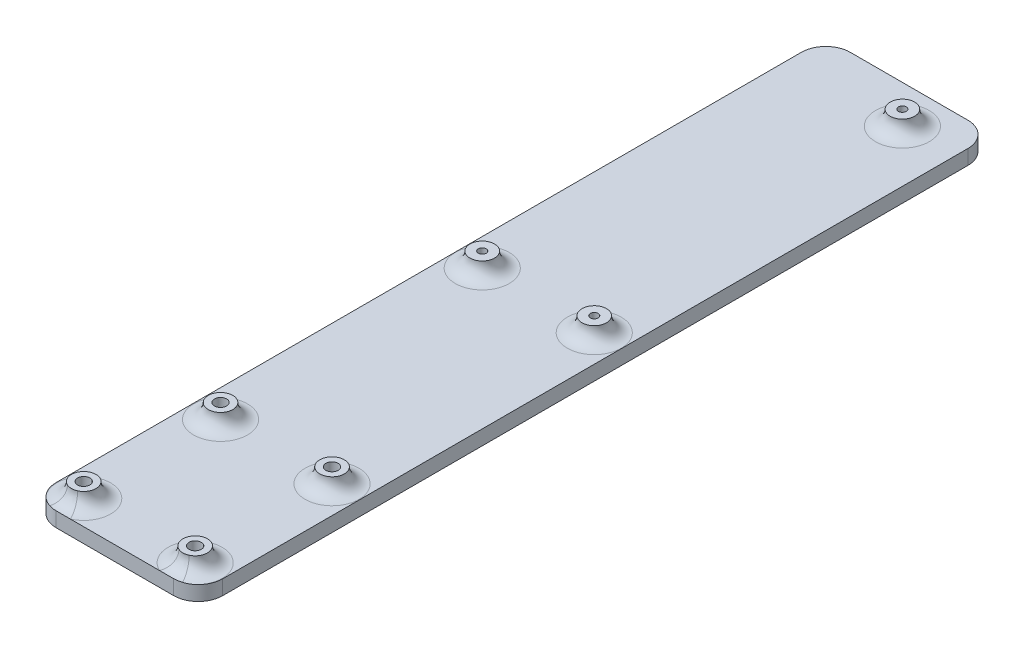
SolidWorks part; units mm, degrees
ref_plane "Front Plane" through (0, 0, 0) normal (0, 0, 1) x (1, 0, 0)
ref_plane "Top Plane" through (0, 0, 0) normal (0, 1, 0) x (1, 0, 0)
ref_plane "Right Plane" through (0, 0, 0) normal (1, 0, 0) x (0, 0, -1)
sketch "Sketch1" plane through (0, 0, 0) normal (0, 1, 0) x (1, 0, 0)
  line L0 (11.4254, -21.605) -> (-11.4346, -21.605) construction
  line L1 (14, -49.075) -> (-14, -49.075)
  line L2 (14, -49.075) -> (14, 49.075)
  line L3 (14, 49.075) -> (-14, 49.075)
  line L4 (-14, -49.075) -> (-14, 49.075)
  line L5 (14, -49.075) -> (-14, 49.075) construction
  line L6 (14, 49.075) -> (-14, -49.075) construction
  line L7 (0, -89.04) -> (0, 0) construction
  line L8 (-11.375, -75.075) -> (11.375, -75.075)
  line L9 (-11.375, -75.075) -> (-11.375, -103.005)
  line L10 (-11.375, -103.005) -> (11.375, -103.005)
  line L11 (11.375, -75.075) -> (11.375, -103.005)
  line L12 (-11.375, -75.075) -> (11.375, -103.005) construction
  line L13 (-11.375, -103.005) -> (11.375, -75.075) construction
  line L15 (-9, -49.075) -> (9, -49.075)
  line L16 (-9, -49.075) -> (-9, -55.075)
  line L17 (-9, -55.075) -> (9, -55.075)
  line L18 (9, -49.075) -> (9, -55.075)
  point P0 (0, 0)
  point P6 (11.4254, -21.605)
  point P7 (-11.4346, -21.605)
  point P10 (0, -89.04)
  point P12 (6.36, 46.345)
  point P22 (0, -55.075)
  dimension "D1" = 28
  dimension "D2" = 98.15
  dimension "D3" = 2.5654
  dimension "D4" = 25.4254
  dimension "D5" = 70.68
  dimension "D6" = 7.64
  dimension "D7" = 2.73
  dimension "D8" = 22.75
  dimension "D9" = 27.93
  dimension "D10" = 20
  dimension "D11" = 18
  dimension "D12" = 6
sketch "Sketch3" plane through (0, 0, 0) normal (0, 1, 0) x (1, 0, 0)
  line L0 (14, 49.075) -> (-14, 49.075) construction
  line L1 (-17, 54.075) -> (17, 54.075)
  line L2 (-17, 54.075) -> (-17, -108.005)
  line L3 (-17, -108.005) -> (17, -108.005)
  line L4 (17, 54.075) -> (17, -108.005)
  line L5 (14, -49.075) -> (14, 49.075) construction
  line L6 (-11.375, -103.005) -> (11.375, -103.005) construction
  line L7 (-14, -49.075) -> (-14, 49.075) construction
  dimension "D1" = 5
  dimension "D2" = 3
  dimension "D3" = 5
  dimension "D4" = 3
extrude "Boss-Extrude1" add sketch "Sketch3" along normal blind 3
sketch "Sketch4" plane through (0, 3, 0) normal (0, 1, 0) x (1, 0, 0)
  circle A0 centre (6.36, 46.345) radius 2.5
  circle A1 centre (-11.4346, -21.605) radius 2.5
  circle A2 centre (11.4254, -21.605) radius 2.5
  circle A3 centre (-11.375, -75.075) radius 2.5
  circle A4 centre (-11.375, -103.005) radius 2.5
  circle A5 centre (11.375, -103.005) radius 2.5
  circle A6 centre (11.375, -75.075) radius 2.5
  dimension "D1" = 5
extrude "Boss-Extrude2" add sketch "Sketch4" along normal blind 3
fillet "Fillet1" radius 3 7 edges at (11.375, 3, 77.575) (11.375, 3, 105.505) (-11.375, 3, 105.505) (-11.375, 3, 77.575) (6.36, 3, -43.845) (11.4254, 3, 24.105) (-11.4346, 3, 24.105)
hole_wizard "Tap Drill for M2x0.4 Tap1" positions "Sketch7" profile "Sketch8" hole size "M2x0.4" standard "ANSI Metric" end condition through all
sketch "Sketch7" plane through (0, 6, 0) normal (0, 1, 0) x (1, 0, 0)
  point P0 (6.36, 46.345)
  point P3 (-11.4346, -21.605)
  point P6 (11.4254, -21.605)
sketch "Sketch8" plane through (6.36, 6, -46.345) normal (1, 0, 0) x (0, 0, 1)
  line L0 (0, 0) -> (0, 6)
  line L1 (0, 6) -> (0.8, 6)
  line L2 (0.8, 6) -> (0.8, 0)
  line L5 (0.8, 0) -> (0, 0)
  line L11 (0, -6.35) -> (0, 107.95) construction
  dimension "Thru Hole Dia." = 1.6
  dimension "Thru Hole Depth" = 6
hole_wizard "Tap Drill for M3x0.5 Tap1" positions "Sketch5" profile "Sketch6" hole size "M3x0.5" standard "ANSI Metric" end condition through all
sketch "Sketch5" plane through (0, 6, 0) normal (0, 1, 0) x (1, 0, 0)
  point P9 (-11.375, -75.075)
  point P12 (-11.375, -103.005)
  point P15 (11.375, -103.005)
  point P18 (11.375, -75.075)
sketch "Sketch6" plane through (-11.375, 6, 75.075) normal (1, 0, 0) x (0, 0, 1)
  line L0 (0, 0) -> (0, 6)
  line L1 (0, 6) -> (1.25, 6)
  line L2 (1.25, 6) -> (1.25, 0)
  line L5 (1.25, 0) -> (0, 0)
  line L11 (0, -6.35) -> (0, 107.95) construction
  dimension "Thru Hole Dia." = 2.5
  dimension "Thru Hole Depth" = 6
fillet "Fillet2" radius 5 4 edges at (-17, 1.5, 108.005) (17, 1.5, 108.005) (17, 1.5, -54.075) (-17, 1.5, -54.075)
